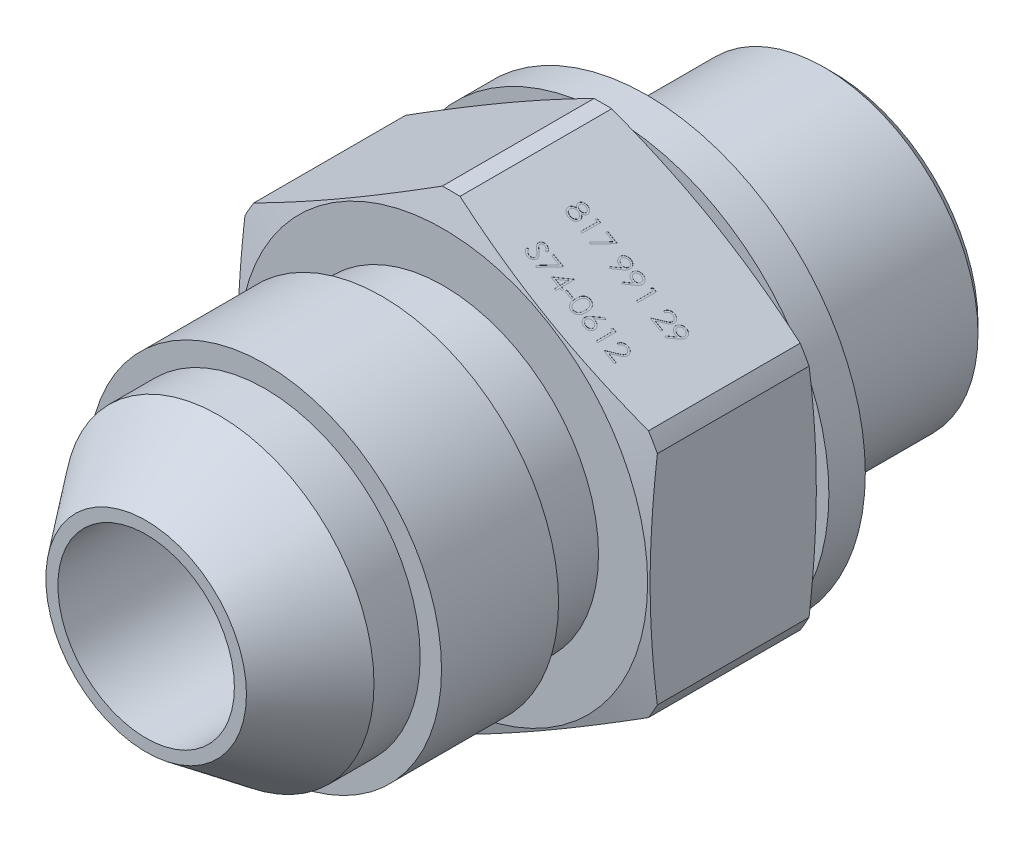
SolidWorks part; units mm, degrees
material "Plain Carbon Steel"
ref_plane "Front Plane" through (0, 0, 0) normal (0, 0, 1) x (1, 0, 0)
ref_plane "Top Plane" through (0, 0, 0) normal (0, 1, 0) x (1, 0, 0)
ref_plane "Right Plane" through (0, 0, 0) normal (1, 0, 0) x (0, 0, -1)
sketch "Sketch1" plane through (0, 0, 0) normal (1, 0, 0) x (0, 0, -1)
  line L0 (0, 0) -> (90.3331, 0) construction
  line L1 (0, 5.4) -> (3.9148, 8.35)
  line L2 (3.9148, 8.35) -> (6.4, 8.35)
  line L3 (6.4, 8.35) -> (6.4, 9.5)
  line L4 (6.4, 9.5) -> (12.7, 9.5)
  line L5 (12.7, 9.5) -> (12.7, 8.35)
  line L6 (12.7, 8.35) -> (16, 8.35)
  line L7 (16, 8.35) -> (16, 10.994)
  line L8 (16.4169, 12.55) -> (24.5831, 12.55)
  line L9 (25, 10.994) -> (25, 8.275)
  line L10 (25, 8.275) -> (36.5, 8.275)
  line L11 (37, 7.775) -> (37, 6.8)
  line L12 (37, 6.8) -> (33.4493, 4.75)
  line L13 (33.4493, 4.75) -> (0, 4.75)
  line L14 (0, 4.75) -> (0, 5.4)
  line L15 (36.5, 8.275) -> (37, 7.775)
  line L16 (16.4169, 12.55) -> (16, 10.994)
  line L17 (24.5831, 12.55) -> (25, 10.994)
  point P14 (37, 8.275)
  dimension "D1" = 25.1
  dimension "D2" = 16.55
  dimension "D3" = 9.5
  dimension "D4" = 13.6
  dimension "D5" = 30
  dimension "D6" = 12
  dimension "D7" = 37
  dimension "D8" = 3.3
  dimension "D9" = 6.4
  dimension "D10" = 16.7
  dimension "D11" = 19
  dimension "D12" = 16
  dimension "D13" = 10.8
  dimension "D14" = 37
  dimension "D15" = 15
  dimension "D16" = 15
  dimension "D18" = 1.556
revolve "Revolve1" add sketch "Sketch1" angle 360 about L0
cosmetic thread "Cosmetic Thread1" parameters "D2"=16.6
sketch "Sketch2" plane through (0, 0, -16) normal (0, 0, 1) x (1, 0, 0)
  line L1 (0, 12.8172) -> (-11.1, 6.4086)
  line L2 (-11.1, 6.4086) -> (-11.1, -6.4086)
  line L3 (-11.1, -6.4086) -> (0, -12.8172)
  line L4 (0, -12.8172) -> (11.1, -6.4086)
  line L5 (11.1, -6.4086) -> (11.1, 6.4086)
  line L6 (11.1, 6.4086) -> (0, 12.8172)
  circle A0 centre (0, 0) radius 11.1 construction
  dimension "D1" = 22.2
extrude "Extrude2" cut sketch "Sketch2" against normal up to surface (9 mm away) flip side to cut up to face at (10.994, 0, -25)
sketch "Sketch3" plane through (0, 0, -25) normal (0, 0, -1) x (-1, 0, 0)
  circle A0 centre (0, 0) radius 11.75
  circle A1 centre (0, 0) radius 9.9
  dimension "D1" = 23.5
  dimension "D2" = 19.8
extrude "Extrude3" add sketch "Sketch3" along normal blind 1.96
sketch "Sketch5" plane through (5.55, 9.6129, 0) normal (0.5, 0.866, 0) x (0.866, -0.5, 0)
  line L0 (-5.7258, 19.8095) -> (5.856, 19.8095) construction
  line L1 (5.856, 16.4169) -> (5.856, 24.5831) construction
  text T0 "817 991 29\r\nS74-0612" font "Century Gothic" height 1
extrude "Cut-Extrude1" cut sketch "Sketch5" against normal blind 0.01
sketch "Sketch6" plane through (0, 0, 0) normal (1, 0, 0) x (0, 0, -1)
  line L0 (0, 0) -> (40.5913, 0) construction
  line L1 (26.96, -11.75) -> (26.96, 11.75) construction
  circle A0 centre (26.16, 9) radius 1.2
  dimension "D1" = 18
  dimension "D2" = 2.4
  dimension "D3" = 0.8
revolve "Revolve2" add sketch "Sketch6" angle 360 about L0
